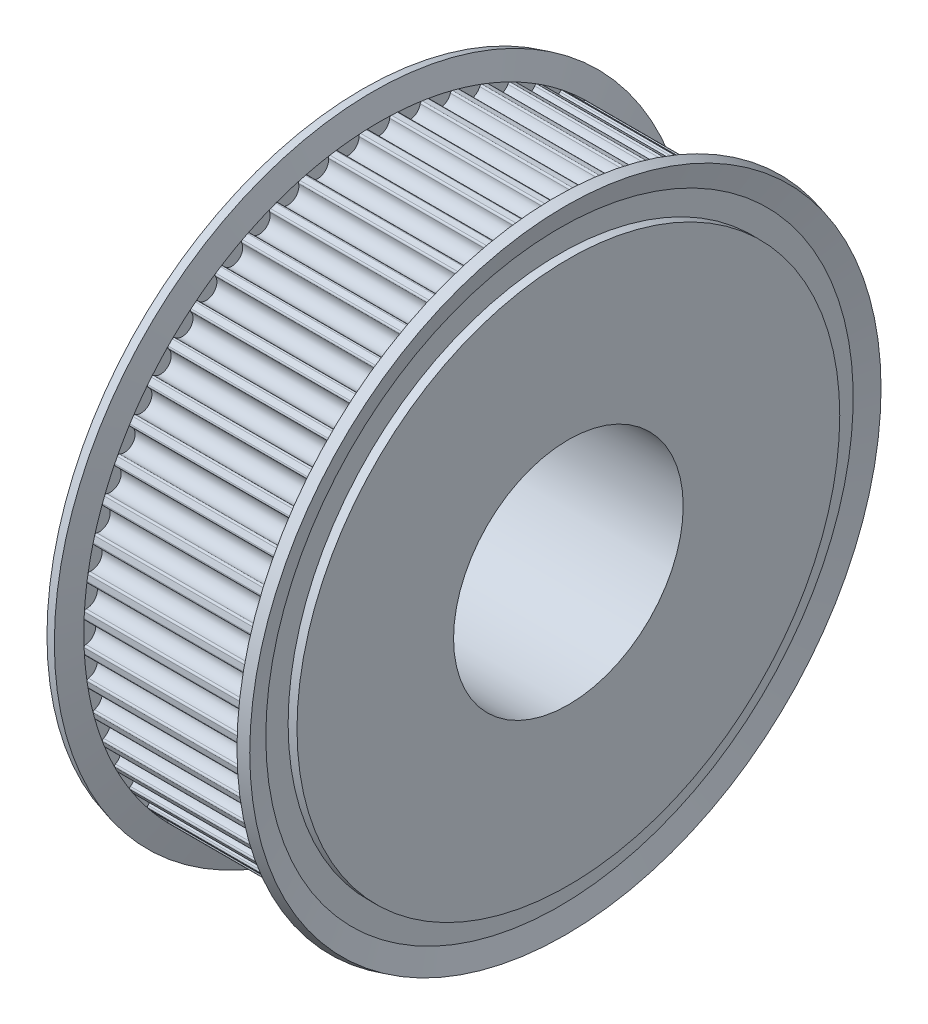
SolidWorks part; units mm, degrees
ref_plane "Front Plane" through (0, 0, 0) normal (0, 0, 1) x (1, 0, 0)
ref_plane "Top Plane" through (0, 0, 0) normal (0, 1, 0) x (1, 0, 0)
ref_plane "Right Plane" through (0, 0, 0) normal (1, 0, 0) x (0, 0, -1)
ref_plane "Plane1" through (0, 0, 0) normal (0, 0, 1) x (1, 0, 0)
sketch "Sketch1" plane through (0, 0, 0) normal (0, 0, 1) x (1, 0, 0)
  line L0 (0, 0) -> (0, 26)
  line L1 (0, 26) -> (0.85, 26)
  line L2 (0.85, 26) -> (0.85, 28.1383)
  line L3 (0.85, 28.1383) -> (0.2865, 30.2412)
  line L4 (0.2865, 30.2412) -> (1.2525, 30.5)
  line L5 (1.2525, 30.5) -> (1.85, 28.27)
  line L6 (1.85, 28.27) -> (18.15, 28.27)
  line L7 (18.15, 28.27) -> (18.7475, 30.5)
  line L8 (18.7475, 30.5) -> (19.7135, 30.2412)
  line L9 (19.7135, 30.2412) -> (19.15, 28.1383)
  line L10 (19.15, 28.1383) -> (19.15, 26)
  line L11 (19.15, 26) -> (20, 26)
  line L12 (20, 26) -> (20, 0)
  line L13 (20, 0) -> (0, 0)
  line L14 (20, 0) -> (0, 0) construction
revolve "Revolve1" add sketch "Sketch1" angle 360 about L14 reverse direction yes
ref_plane "Plane2" through (10, 0, 0) normal (1, 0, 0) x (0, 0, -1)
sketch "Sketch2" plane through (10, 0, 0) normal (1, 0, 0) x (0, 0, -1)
  line L0 (-1.2204, 28.624) -> (-1.2042, 28.2443)
  line L1 (1.2042, 28.2443) -> (1.2204, 28.624)
  arc A0 (-1.2042, 28.2443) -> (-1.0274, 28.0866) centre (-1.1969, 28.0745) cw
  arc A1 (-1.0274, 28.0866) -> (1.0274, 28.0866) centre (0, 28.16) ccw
  arc A2 (1.0274, 28.0866) -> (1.2042, 28.2443) centre (1.1969, 28.0745) cw
  arc A3 (1.2204, 28.624) -> (-1.2204, 28.624) centre (0, 0) ccw
extrude "Cut-Extrude1" cut sketch "Sketch2" against normal blind 8.15 and the other way blind 8.15
ref_plane "Plane3" through (10, 0, 0) normal (1, 0, 0) x (0, 0, -1)
sketch "Sketch3" plane through (10, 0, 0) normal (1, 0, 0) x (0, 0, -1)
  line L0 (-4.2057, 28.3396) -> (-4.1499, 27.9637)
  line L1 (-1.7547, 28.2155) -> (-1.7783, 28.5948)
  arc A0 (-4.1499, 27.9637) -> (-3.9576, 27.8254) centre (-4.125, 27.7956) cw
  arc A1 (-3.9576, 27.8254) -> (-1.9141, 28.0401) centre (-2.9435, 28.0057) ccw
  arc A2 (-1.9141, 28.0401) -> (-1.7547, 28.2155) centre (-1.7442, 28.0458) cw
  arc A3 (-1.7783, 28.5948) -> (-4.2057, 28.3396) centre (0, 0) ccw
extrude "Cut-Extrude2" cut sketch "Sketch3" against normal blind 8.15 and the other way blind 8.15
ref_plane "Plane4" through (10, 0, 0) normal (1, 0, 0) x (0, 0, -1)
sketch "Sketch4" plane through (10, 0, 0) normal (1, 0, 0) x (0, 0, -1)
  line L0 (-7.145, 27.7448) -> (-7.0502, 27.3768)
  line L1 (-4.6945, 27.8775) -> (-4.7576, 28.2522)
  arc A0 (-7.0502, 27.3768) -> (-6.8445, 27.2592) centre (-7.0078, 27.2121) cw
  arc A1 (-6.8445, 27.2592) -> (-4.8346, 27.6865) centre (-5.8548, 27.5446) ccw
  arc A2 (-4.8346, 27.6865) -> (-4.6945, 27.8775) centre (-4.6662, 27.7099) cw
  arc A3 (-4.7576, 28.2522) -> (-7.145, 27.7448) centre (0, 0) ccw
extrude "Cut-Extrude3" cut sketch "Sketch4" against normal blind 8.15 and the other way blind 8.15
ref_plane "Plane5" through (10, 0, 0) normal (1, 0, 0) x (0, 0, -1)
sketch "Sketch5" plane through (10, 0, 0) normal (1, 0, 0) x (0, 0, -1)
  line L0 (-10.0059, 26.8459) -> (-9.8732, 26.4898)
  line L1 (-7.5827, 27.2341) -> (-7.6847, 27.6002)
  arc A0 (-9.8732, 26.4898) -> (-9.6563, 26.3945) centre (-9.8139, 26.3306) cw
  arc A1 (-9.6563, 26.3945) -> (-7.7021, 27.0294) centre (-8.7019, 26.7818) ccw
  arc A2 (-7.7021, 27.0294) -> (-7.5827, 27.2341) centre (-7.5371, 27.0703) cw
  arc A3 (-7.6847, 27.6002) -> (-10.0059, 26.8459) centre (0, 0) ccw
extrude "Cut-Extrude4" cut sketch "Sketch5" against normal blind 8.15 and the other way blind 8.15
ref_plane "Plane6" through (10, 0, 0) normal (1, 0, 0) x (0, 0, -1)
sketch "Sketch6" plane through (10, 0, 0) normal (1, 0, 0) x (0, 0, -1)
  line L0 (-12.7573, 25.6529) -> (-12.5881, 25.3127)
  line L1 (-10.3879, 26.2923) -> (-10.5276, 26.6457)
  arc A0 (-12.5881, 25.3127) -> (-12.3624, 25.2405) centre (-12.5124, 25.1605) cw
  arc A1 (-12.3624, 25.2405) -> (-10.4853, 26.0763) centre (-11.4537, 25.7254) ccw
  arc A2 (-10.4853, 26.0763) -> (-10.3879, 26.2923) centre (-10.3255, 26.1342) cw
  arc A3 (-10.5276, 26.6457) -> (-12.7573, 25.6529) centre (0, 0) ccw
extrude "Cut-Extrude5" cut sketch "Sketch6" against normal blind 8.15 and the other way blind 8.15
ref_plane "Plane7" through (10, 0, 0) normal (1, 0, 0) x (0, 0, -1)
sketch "Sketch7" plane through (10, 0, 0) normal (1, 0, 0) x (0, 0, -1)
  line L0 (-15.3689, 24.1789) -> (-15.165, 23.8582)
  line L1 (-13.0793, 25.0624) -> (-13.2551, 25.3993)
  arc A0 (-15.165, 23.8582) -> (-14.933, 23.81) centre (-15.0738, 23.7148) cw
  arc A1 (-14.933, 23.81) -> (-13.1536, 24.8374) centre (-14.08, 24.3873) ccw
  arc A2 (-13.1536, 24.8374) -> (-13.0793, 25.0624) centre (-13.0007, 24.9117) cw
  arc A3 (-13.2551, 25.3993) -> (-15.3689, 24.1789) centre (0, 0) ccw
extrude "Cut-Extrude6" cut sketch "Sketch7" against normal blind 8.15 and the other way blind 8.15
ref_plane "Plane8" through (10, 0, 0) normal (1, 0, 0) x (0, 0, -1)
sketch "Sketch8" plane through (10, 0, 0) normal (1, 0, 0) x (0, 0, -1)
  line L0 (-17.8121, 22.44) -> (-17.5758, 22.1423)
  line L1 (-15.6274, 23.558) -> (-15.8375, 23.8746)
  arc A0 (-17.5758, 22.1423) -> (-17.3401, 22.1187) centre (-17.4701, 22.0092) cw
  arc A1 (-17.3401, 22.1187) -> (-15.6777, 23.3264) centre (-16.552, 22.7819) ccw
  arc A2 (-15.6777, 23.3264) -> (-15.6274, 23.558) centre (-15.5334, 23.4163) cw
  arc A3 (-15.8375, 23.8746) -> (-17.8121, 22.44) centre (0, 0) ccw
extrude "Cut-Extrude7" cut sketch "Sketch8" against normal blind 8.15 and the other way blind 8.15
ref_plane "Plane9" through (10, 0, 0) normal (1, 0, 0) x (0, 0, -1)
sketch "Sketch9" plane through (10, 0, 0) normal (1, 0, 0) x (0, 0, -1)
  line L0 (-20.0601, 20.4552) -> (-19.794, 20.1839)
  line L1 (-18.0043, 21.7954) -> (-18.2463, 22.0884)
  arc A0 (-19.794, 20.1839) -> (-19.5571, 20.185) centre (-19.675, 20.0625) cw
  arc A1 (-19.5571, 20.185) -> (-18.0301, 21.5599) centre (-18.8427, 20.927) ccw
  arc A2 (-18.0301, 21.5599) -> (-18.0043, 21.7954) centre (-17.896, 21.6643) cw
  arc A3 (-18.2463, 22.0884) -> (-20.0601, 20.4552) centre (0, 0) ccw
extrude "Cut-Extrude8" cut sketch "Sketch9" against normal blind 8.15 and the other way blind 8.15
ref_plane "Plane10" through (10, 0, 0) normal (1, 0, 0) x (0, 0, -1)
sketch "Sketch10" plane through (10, 0, 0) normal (1, 0, 0) x (0, 0, -1)
  line L0 (-22.0884, 18.2463) -> (-21.7954, 18.0043)
  line L1 (-20.1839, 19.794) -> (-20.4552, 20.0601)
  arc A0 (-21.7954, 18.0043) -> (-21.5599, 18.0301) centre (-21.6643, 17.896) cw
  arc A1 (-21.5599, 18.0301) -> (-20.185, 19.5571) centre (-20.927, 18.8427) ccw
  arc A2 (-20.185, 19.5571) -> (-20.1839, 19.794) centre (-20.0625, 19.675) cw
  arc A3 (-20.4552, 20.0601) -> (-22.0884, 18.2463) centre (0, 0) ccw
extrude "Cut-Extrude9" cut sketch "Sketch10" against normal blind 8.15 and the other way blind 8.15
ref_plane "Plane11" through (10, 0, 0) normal (1, 0, 0) x (0, 0, -1)
sketch "Sketch11" plane through (10, 0, 0) normal (1, 0, 0) x (0, 0, -1)
  line L0 (-23.8746, 15.8375) -> (-23.558, 15.6274)
  line L1 (-22.1423, 17.5758) -> (-22.44, 17.8121)
  arc A0 (-23.558, 15.6274) -> (-23.3264, 15.6777) centre (-23.4163, 15.5334) cw
  arc A1 (-23.3264, 15.6777) -> (-22.1187, 17.3401) centre (-22.7819, 16.552) ccw
  arc A2 (-22.1187, 17.3401) -> (-22.1423, 17.5758) centre (-22.0092, 17.4701) cw
  arc A3 (-22.44, 17.8121) -> (-23.8746, 15.8375) centre (0, 0) ccw
extrude "Cut-Extrude10" cut sketch "Sketch11" against normal blind 8.15 and the other way blind 8.15
ref_plane "Plane12" through (10, 0, 0) normal (1, 0, 0) x (0, 0, -1)
sketch "Sketch12" plane through (10, 0, 0) normal (1, 0, 0) x (0, 0, -1)
  line L0 (-25.3993, 13.2551) -> (-25.0624, 13.0793)
  line L1 (-23.8582, 15.165) -> (-24.1789, 15.3689)
  arc A0 (-25.0624, 13.0793) -> (-24.8374, 13.1536) centre (-24.9117, 13.0007) cw
  arc A1 (-24.8374, 13.1536) -> (-23.81, 14.933) centre (-24.3873, 14.08) ccw
  arc A2 (-23.81, 14.933) -> (-23.8582, 15.165) centre (-23.7148, 15.0738) cw
  arc A3 (-24.1789, 15.3689) -> (-25.3993, 13.2551) centre (0, 0) ccw
extrude "Cut-Extrude11" cut sketch "Sketch12" against normal blind 8.15 and the other way blind 8.15
ref_plane "Plane13" through (10, 0, 0) normal (1, 0, 0) x (0, 0, -1)
sketch "Sketch13" plane through (10, 0, 0) normal (1, 0, 0) x (0, 0, -1)
  line L0 (-26.6457, 10.5276) -> (-26.2923, 10.3879)
  line L1 (-25.3127, 12.5881) -> (-25.6529, 12.7573)
  arc A0 (-26.2923, 10.3879) -> (-26.0763, 10.4853) centre (-26.1342, 10.3255) cw
  arc A1 (-26.0763, 10.4853) -> (-25.2405, 12.3624) centre (-25.7254, 11.4537) ccw
  arc A2 (-25.2405, 12.3624) -> (-25.3127, 12.5881) centre (-25.1605, 12.5124) cw
  arc A3 (-25.6529, 12.7573) -> (-26.6457, 10.5276) centre (0, 0) ccw
extrude "Cut-Extrude12" cut sketch "Sketch13" against normal blind 8.15 and the other way blind 8.15
ref_plane "Plane14" through (10, 0, 0) normal (1, 0, 0) x (0, 0, -1)
sketch "Sketch14" plane through (10, 0, 0) normal (1, 0, 0) x (0, 0, -1)
  line L0 (-27.6002, 7.6847) -> (-27.2341, 7.5827)
  line L1 (-26.4898, 9.8732) -> (-26.8459, 10.0059)
  arc A0 (-27.2341, 7.5827) -> (-27.0294, 7.7021) centre (-27.0703, 7.5371) cw
  arc A1 (-27.0294, 7.7021) -> (-26.3945, 9.6563) centre (-26.7818, 8.7019) ccw
  arc A2 (-26.3945, 9.6563) -> (-26.4898, 9.8732) centre (-26.3306, 9.8139) cw
  arc A3 (-26.8459, 10.0059) -> (-27.6002, 7.6847) centre (0, 0) ccw
extrude "Cut-Extrude13" cut sketch "Sketch14" against normal blind 8.15 and the other way blind 8.15
ref_plane "Plane15" through (10, 0, 0) normal (1, 0, 0) x (0, 0, -1)
sketch "Sketch15" plane through (10, 0, 0) normal (1, 0, 0) x (0, 0, -1)
  line L0 (-28.2522, 4.7576) -> (-27.8775, 4.6945)
  line L1 (-27.3768, 7.0502) -> (-27.7448, 7.145)
  arc A0 (-27.8775, 4.6945) -> (-27.6865, 4.8346) centre (-27.7099, 4.6662) cw
  arc A1 (-27.6865, 4.8346) -> (-27.2592, 6.8445) centre (-27.5446, 5.8548) ccw
  arc A2 (-27.2592, 6.8445) -> (-27.3768, 7.0502) centre (-27.2121, 7.0078) cw
  arc A3 (-27.7448, 7.145) -> (-28.2522, 4.7576) centre (0, 0) ccw
extrude "Cut-Extrude14" cut sketch "Sketch15" against normal blind 8.15 and the other way blind 8.15
ref_plane "Plane16" through (10, 0, 0) normal (1, 0, 0) x (0, 0, -1)
sketch "Sketch16" plane through (10, 0, 0) normal (1, 0, 0) x (0, 0, -1)
  line L0 (-28.5948, 1.7783) -> (-28.2155, 1.7547)
  line L1 (-27.9637, 4.1499) -> (-28.3396, 4.2057)
  arc A0 (-28.2155, 1.7547) -> (-28.0401, 1.9141) centre (-28.0458, 1.7442) cw
  arc A1 (-28.0401, 1.9141) -> (-27.8254, 3.9576) centre (-28.0057, 2.9435) ccw
  arc A2 (-27.8254, 3.9576) -> (-27.9637, 4.1499) centre (-27.7956, 4.125) cw
  arc A3 (-28.3396, 4.2057) -> (-28.5948, 1.7783) centre (0, 0) ccw
extrude "Cut-Extrude15" cut sketch "Sketch16" against normal blind 8.15 and the other way blind 8.15
ref_plane "Plane17" through (10, 0, 0) normal (1, 0, 0) x (0, 0, -1)
sketch "Sketch17" plane through (10, 0, 0) normal (1, 0, 0) x (0, 0, -1)
  line L0 (-28.624, -1.2204) -> (-28.2443, -1.2042)
  line L1 (-28.2443, 1.2042) -> (-28.624, 1.2204)
  arc A0 (-28.2443, -1.2042) -> (-28.0866, -1.0274) centre (-28.0745, -1.1969) cw
  arc A1 (-28.0866, -1.0274) -> (-28.0866, 1.0274) centre (-28.16, 0) ccw
  arc A2 (-28.0866, 1.0274) -> (-28.2443, 1.2042) centre (-28.0745, 1.1969) cw
  arc A3 (-28.624, 1.2204) -> (-28.624, -1.2204) centre (0, 0) ccw
extrude "Cut-Extrude16" cut sketch "Sketch17" against normal blind 8.15 and the other way blind 8.15
ref_plane "Plane18" through (10, 0, 0) normal (1, 0, 0) x (0, 0, -1)
sketch "Sketch18" plane through (10, 0, 0) normal (1, 0, 0) x (0, 0, -1)
  line L0 (-28.3396, -4.2057) -> (-27.9637, -4.1499)
  line L1 (-28.2155, -1.7547) -> (-28.5948, -1.7783)
  arc A0 (-27.9637, -4.1499) -> (-27.8254, -3.9576) centre (-27.7956, -4.125) cw
  arc A1 (-27.8254, -3.9576) -> (-28.0401, -1.9141) centre (-28.0057, -2.9435) ccw
  arc A2 (-28.0401, -1.9141) -> (-28.2155, -1.7547) centre (-28.0458, -1.7442) cw
  arc A3 (-28.5948, -1.7783) -> (-28.3396, -4.2057) centre (0, 0) ccw
extrude "Cut-Extrude17" cut sketch "Sketch18" against normal blind 8.15 and the other way blind 8.15
ref_plane "Plane19" through (10, 0, 0) normal (1, 0, 0) x (0, 0, -1)
sketch "Sketch19" plane through (10, 0, 0) normal (1, 0, 0) x (0, 0, -1)
  line L0 (-27.7448, -7.145) -> (-27.3768, -7.0502)
  line L1 (-27.8775, -4.6945) -> (-28.2522, -4.7576)
  arc A0 (-27.3768, -7.0502) -> (-27.2592, -6.8445) centre (-27.2121, -7.0078) cw
  arc A1 (-27.2592, -6.8445) -> (-27.6865, -4.8346) centre (-27.5446, -5.8548) ccw
  arc A2 (-27.6865, -4.8346) -> (-27.8775, -4.6945) centre (-27.7099, -4.6662) cw
  arc A3 (-28.2522, -4.7576) -> (-27.7448, -7.145) centre (0, 0) ccw
extrude "Cut-Extrude18" cut sketch "Sketch19" against normal blind 8.15 and the other way blind 8.15
ref_plane "Plane20" through (10, 0, 0) normal (1, 0, 0) x (0, 0, -1)
sketch "Sketch20" plane through (10, 0, 0) normal (1, 0, 0) x (0, 0, -1)
  line L0 (-26.8459, -10.0059) -> (-26.4898, -9.8732)
  line L1 (-27.2341, -7.5827) -> (-27.6002, -7.6847)
  arc A0 (-26.4898, -9.8732) -> (-26.3945, -9.6563) centre (-26.3306, -9.8139) cw
  arc A1 (-26.3945, -9.6563) -> (-27.0294, -7.7021) centre (-26.7818, -8.7019) ccw
  arc A2 (-27.0294, -7.7021) -> (-27.2341, -7.5827) centre (-27.0703, -7.5371) cw
  arc A3 (-27.6002, -7.6847) -> (-26.8459, -10.0059) centre (0, 0) ccw
extrude "Cut-Extrude19" cut sketch "Sketch20" against normal blind 8.15 and the other way blind 8.15
ref_plane "Plane21" through (10, 0, 0) normal (1, 0, 0) x (0, 0, -1)
sketch "Sketch21" plane through (10, 0, 0) normal (1, 0, 0) x (0, 0, -1)
  line L0 (-25.6529, -12.7573) -> (-25.3127, -12.5881)
  line L1 (-26.2923, -10.3879) -> (-26.6457, -10.5276)
  arc A0 (-25.3127, -12.5881) -> (-25.2405, -12.3624) centre (-25.1605, -12.5124) cw
  arc A1 (-25.2405, -12.3624) -> (-26.0763, -10.4853) centre (-25.7254, -11.4537) ccw
  arc A2 (-26.0763, -10.4853) -> (-26.2923, -10.3879) centre (-26.1342, -10.3255) cw
  arc A3 (-26.6457, -10.5276) -> (-25.6529, -12.7573) centre (0, 0) ccw
extrude "Cut-Extrude20" cut sketch "Sketch21" against normal blind 8.15 and the other way blind 8.15
ref_plane "Plane22" through (10, 0, 0) normal (1, 0, 0) x (0, 0, -1)
sketch "Sketch22" plane through (10, 0, 0) normal (1, 0, 0) x (0, 0, -1)
  line L0 (-24.1789, -15.3689) -> (-23.8582, -15.165)
  line L1 (-25.0624, -13.0793) -> (-25.3993, -13.2551)
  arc A0 (-23.8582, -15.165) -> (-23.81, -14.933) centre (-23.7148, -15.0738) cw
  arc A1 (-23.81, -14.933) -> (-24.8374, -13.1536) centre (-24.3873, -14.08) ccw
  arc A2 (-24.8374, -13.1536) -> (-25.0624, -13.0793) centre (-24.9117, -13.0007) cw
  arc A3 (-25.3993, -13.2551) -> (-24.1789, -15.3689) centre (0, 0) ccw
extrude "Cut-Extrude21" cut sketch "Sketch22" against normal blind 8.15 and the other way blind 8.15
ref_plane "Plane23" through (10, 0, 0) normal (1, 0, 0) x (0, 0, -1)
sketch "Sketch23" plane through (10, 0, 0) normal (1, 0, 0) x (0, 0, -1)
  line L0 (-22.44, -17.8121) -> (-22.1423, -17.5758)
  line L1 (-23.558, -15.6274) -> (-23.8746, -15.8375)
  arc A0 (-22.1423, -17.5758) -> (-22.1187, -17.3401) centre (-22.0092, -17.4701) cw
  arc A1 (-22.1187, -17.3401) -> (-23.3264, -15.6777) centre (-22.7819, -16.552) ccw
  arc A2 (-23.3264, -15.6777) -> (-23.558, -15.6274) centre (-23.4163, -15.5334) cw
  arc A3 (-23.8746, -15.8375) -> (-22.44, -17.8121) centre (0, 0) ccw
extrude "Cut-Extrude22" cut sketch "Sketch23" against normal blind 8.15 and the other way blind 8.15
ref_plane "Plane24" through (10, 0, 0) normal (1, 0, 0) x (0, 0, -1)
sketch "Sketch24" plane through (10, 0, 0) normal (1, 0, 0) x (0, 0, -1)
  line L0 (-20.4552, -20.0601) -> (-20.1839, -19.794)
  line L1 (-21.7954, -18.0043) -> (-22.0884, -18.2463)
  arc A0 (-20.1839, -19.794) -> (-20.185, -19.5571) centre (-20.0625, -19.675) cw
  arc A1 (-20.185, -19.5571) -> (-21.5599, -18.0301) centre (-20.927, -18.8427) ccw
  arc A2 (-21.5599, -18.0301) -> (-21.7954, -18.0043) centre (-21.6643, -17.896) cw
  arc A3 (-22.0884, -18.2463) -> (-20.4552, -20.0601) centre (0, 0) ccw
extrude "Cut-Extrude23" cut sketch "Sketch24" against normal blind 8.15 and the other way blind 8.15
ref_plane "Plane25" through (10, 0, 0) normal (1, 0, 0) x (0, 0, -1)
sketch "Sketch25" plane through (10, 0, 0) normal (1, 0, 0) x (0, 0, -1)
  line L0 (-18.2463, -22.0884) -> (-18.0043, -21.7954)
  line L1 (-19.794, -20.1839) -> (-20.0601, -20.4552)
  arc A0 (-18.0043, -21.7954) -> (-18.0301, -21.5599) centre (-17.896, -21.6643) cw
  arc A1 (-18.0301, -21.5599) -> (-19.5571, -20.185) centre (-18.8427, -20.927) ccw
  arc A2 (-19.5571, -20.185) -> (-19.794, -20.1839) centre (-19.675, -20.0625) cw
  arc A3 (-20.0601, -20.4552) -> (-18.2463, -22.0884) centre (0, 0) ccw
extrude "Cut-Extrude24" cut sketch "Sketch25" against normal blind 8.15 and the other way blind 8.15
ref_plane "Plane26" through (10, 0, 0) normal (1, 0, 0) x (0, 0, -1)
sketch "Sketch26" plane through (10, 0, 0) normal (1, 0, 0) x (0, 0, -1)
  line L0 (-15.8375, -23.8746) -> (-15.6274, -23.558)
  line L1 (-17.5758, -22.1423) -> (-17.8121, -22.44)
  arc A0 (-15.6274, -23.558) -> (-15.6777, -23.3264) centre (-15.5334, -23.4163) cw
  arc A1 (-15.6777, -23.3264) -> (-17.3401, -22.1187) centre (-16.552, -22.7819) ccw
  arc A2 (-17.3401, -22.1187) -> (-17.5758, -22.1423) centre (-17.4701, -22.0092) cw
  arc A3 (-17.8121, -22.44) -> (-15.8375, -23.8746) centre (0, 0) ccw
extrude "Cut-Extrude25" cut sketch "Sketch26" against normal blind 8.15 and the other way blind 8.15
ref_plane "Plane27" through (10, 0, 0) normal (1, 0, 0) x (0, 0, -1)
sketch "Sketch27" plane through (10, 0, 0) normal (1, 0, 0) x (0, 0, -1)
  line L0 (-13.2551, -25.3993) -> (-13.0793, -25.0624)
  line L1 (-15.165, -23.8582) -> (-15.3689, -24.1789)
  arc A0 (-13.0793, -25.0624) -> (-13.1536, -24.8374) centre (-13.0007, -24.9117) cw
  arc A1 (-13.1536, -24.8374) -> (-14.933, -23.81) centre (-14.08, -24.3873) ccw
  arc A2 (-14.933, -23.81) -> (-15.165, -23.8582) centre (-15.0738, -23.7148) cw
  arc A3 (-15.3689, -24.1789) -> (-13.2551, -25.3993) centre (0, 0) ccw
extrude "Cut-Extrude26" cut sketch "Sketch27" against normal blind 8.15 and the other way blind 8.15
ref_plane "Plane28" through (10, 0, 0) normal (1, 0, 0) x (0, 0, -1)
sketch "Sketch28" plane through (10, 0, 0) normal (1, 0, 0) x (0, 0, -1)
  line L0 (-10.5276, -26.6457) -> (-10.3879, -26.2923)
  line L1 (-12.5881, -25.3127) -> (-12.7573, -25.6529)
  arc A0 (-10.3879, -26.2923) -> (-10.4853, -26.0763) centre (-10.3255, -26.1342) cw
  arc A1 (-10.4853, -26.0763) -> (-12.3624, -25.2405) centre (-11.4537, -25.7254) ccw
  arc A2 (-12.3624, -25.2405) -> (-12.5881, -25.3127) centre (-12.5124, -25.1605) cw
  arc A3 (-12.7573, -25.6529) -> (-10.5276, -26.6457) centre (0, 0) ccw
extrude "Cut-Extrude27" cut sketch "Sketch28" against normal blind 8.15 and the other way blind 8.15
ref_plane "Plane29" through (10, 0, 0) normal (1, 0, 0) x (0, 0, -1)
sketch "Sketch29" plane through (10, 0, 0) normal (1, 0, 0) x (0, 0, -1)
  line L0 (-7.6847, -27.6002) -> (-7.5827, -27.2341)
  line L1 (-9.8732, -26.4898) -> (-10.0059, -26.8459)
  arc A0 (-7.5827, -27.2341) -> (-7.7021, -27.0294) centre (-7.5371, -27.0703) cw
  arc A1 (-7.7021, -27.0294) -> (-9.6563, -26.3945) centre (-8.7019, -26.7818) ccw
  arc A2 (-9.6563, -26.3945) -> (-9.8732, -26.4898) centre (-9.8139, -26.3306) cw
  arc A3 (-10.0059, -26.8459) -> (-7.6847, -27.6002) centre (0, 0) ccw
extrude "Cut-Extrude28" cut sketch "Sketch29" against normal blind 8.15 and the other way blind 8.15
ref_plane "Plane30" through (10, 0, 0) normal (1, 0, 0) x (0, 0, -1)
sketch "Sketch30" plane through (10, 0, 0) normal (1, 0, 0) x (0, 0, -1)
  line L0 (-4.7576, -28.2522) -> (-4.6945, -27.8775)
  line L1 (-7.0502, -27.3768) -> (-7.145, -27.7448)
  arc A0 (-4.6945, -27.8775) -> (-4.8346, -27.6865) centre (-4.6662, -27.7099) cw
  arc A1 (-4.8346, -27.6865) -> (-6.8445, -27.2592) centre (-5.8548, -27.5446) ccw
  arc A2 (-6.8445, -27.2592) -> (-7.0502, -27.3768) centre (-7.0078, -27.2121) cw
  arc A3 (-7.145, -27.7448) -> (-4.7576, -28.2522) centre (0, 0) ccw
extrude "Cut-Extrude29" cut sketch "Sketch30" against normal blind 8.15 and the other way blind 8.15
ref_plane "Plane31" through (10, 0, 0) normal (1, 0, 0) x (0, 0, -1)
sketch "Sketch31" plane through (10, 0, 0) normal (1, 0, 0) x (0, 0, -1)
  line L0 (-1.7783, -28.5948) -> (-1.7547, -28.2155)
  line L1 (-4.1499, -27.9637) -> (-4.2057, -28.3396)
  arc A0 (-1.7547, -28.2155) -> (-1.9141, -28.0401) centre (-1.7442, -28.0458) cw
  arc A1 (-1.9141, -28.0401) -> (-3.9576, -27.8254) centre (-2.9435, -28.0057) ccw
  arc A2 (-3.9576, -27.8254) -> (-4.1499, -27.9637) centre (-4.125, -27.7956) cw
  arc A3 (-4.2057, -28.3396) -> (-1.7783, -28.5948) centre (0, 0) ccw
extrude "Cut-Extrude30" cut sketch "Sketch31" against normal blind 8.15 and the other way blind 8.15
ref_plane "Plane32" through (10, 0, 0) normal (1, 0, 0) x (0, 0, -1)
sketch "Sketch32" plane through (10, 0, 0) normal (1, 0, 0) x (0, 0, -1)
  line L0 (1.2204, -28.624) -> (1.2042, -28.2443)
  line L1 (-1.2042, -28.2443) -> (-1.2204, -28.624)
  arc A0 (1.2042, -28.2443) -> (1.0274, -28.0866) centre (1.1969, -28.0745) cw
  arc A1 (1.0274, -28.0866) -> (-1.0274, -28.0866) centre (0, -28.16) ccw
  arc A2 (-1.0274, -28.0866) -> (-1.2042, -28.2443) centre (-1.1969, -28.0745) cw
  arc A3 (-1.2204, -28.624) -> (1.2204, -28.624) centre (0, 0) ccw
extrude "Cut-Extrude31" cut sketch "Sketch32" against normal blind 8.15 and the other way blind 8.15
ref_plane "Plane33" through (10, 0, 0) normal (1, 0, 0) x (0, 0, -1)
sketch "Sketch33" plane through (10, 0, 0) normal (1, 0, 0) x (0, 0, -1)
  line L0 (4.2057, -28.3396) -> (4.1499, -27.9637)
  line L1 (1.7547, -28.2155) -> (1.7783, -28.5948)
  arc A0 (4.1499, -27.9637) -> (3.9576, -27.8254) centre (4.125, -27.7956) cw
  arc A1 (3.9576, -27.8254) -> (1.9141, -28.0401) centre (2.9435, -28.0057) ccw
  arc A2 (1.9141, -28.0401) -> (1.7547, -28.2155) centre (1.7442, -28.0458) cw
  arc A3 (1.7783, -28.5948) -> (4.2057, -28.3396) centre (0, 0) ccw
extrude "Cut-Extrude32" cut sketch "Sketch33" against normal blind 8.15 and the other way blind 8.15
ref_plane "Plane34" through (10, 0, 0) normal (1, 0, 0) x (0, 0, -1)
sketch "Sketch34" plane through (10, 0, 0) normal (1, 0, 0) x (0, 0, -1)
  line L0 (7.145, -27.7448) -> (7.0502, -27.3768)
  line L1 (4.6945, -27.8775) -> (4.7576, -28.2522)
  arc A0 (7.0502, -27.3768) -> (6.8445, -27.2592) centre (7.0078, -27.2121) cw
  arc A1 (6.8445, -27.2592) -> (4.8346, -27.6865) centre (5.8548, -27.5446) ccw
  arc A2 (4.8346, -27.6865) -> (4.6945, -27.8775) centre (4.6662, -27.7099) cw
  arc A3 (4.7576, -28.2522) -> (7.145, -27.7448) centre (0, 0) ccw
extrude "Cut-Extrude33" cut sketch "Sketch34" against normal blind 8.15 and the other way blind 8.15
ref_plane "Plane35" through (10, 0, 0) normal (1, 0, 0) x (0, 0, -1)
sketch "Sketch35" plane through (10, 0, 0) normal (1, 0, 0) x (0, 0, -1)
  line L0 (10.0059, -26.8459) -> (9.8732, -26.4898)
  line L1 (7.5827, -27.2341) -> (7.6847, -27.6002)
  arc A0 (9.8732, -26.4898) -> (9.6563, -26.3945) centre (9.8139, -26.3306) cw
  arc A1 (9.6563, -26.3945) -> (7.7021, -27.0294) centre (8.7019, -26.7818) ccw
  arc A2 (7.7021, -27.0294) -> (7.5827, -27.2341) centre (7.5371, -27.0703) cw
  arc A3 (7.6847, -27.6002) -> (10.0059, -26.8459) centre (0, 0) ccw
extrude "Cut-Extrude34" cut sketch "Sketch35" against normal blind 8.15 and the other way blind 8.15
ref_plane "Plane36" through (10, 0, 0) normal (1, 0, 0) x (0, 0, -1)
sketch "Sketch36" plane through (10, 0, 0) normal (1, 0, 0) x (0, 0, -1)
  line L0 (12.7573, -25.6529) -> (12.5881, -25.3127)
  line L1 (10.3879, -26.2923) -> (10.5276, -26.6457)
  arc A0 (12.5881, -25.3127) -> (12.3624, -25.2405) centre (12.5124, -25.1605) cw
  arc A1 (12.3624, -25.2405) -> (10.4853, -26.0763) centre (11.4537, -25.7254) ccw
  arc A2 (10.4853, -26.0763) -> (10.3879, -26.2923) centre (10.3255, -26.1342) cw
  arc A3 (10.5276, -26.6457) -> (12.7573, -25.6529) centre (0, 0) ccw
extrude "Cut-Extrude35" cut sketch "Sketch36" against normal blind 8.15 and the other way blind 8.15
ref_plane "Plane37" through (10, 0, 0) normal (1, 0, 0) x (0, 0, -1)
sketch "Sketch37" plane through (10, 0, 0) normal (1, 0, 0) x (0, 0, -1)
  line L0 (15.3689, -24.1789) -> (15.165, -23.8582)
  line L1 (13.0793, -25.0624) -> (13.2551, -25.3993)
  arc A0 (15.165, -23.8582) -> (14.933, -23.81) centre (15.0738, -23.7148) cw
  arc A1 (14.933, -23.81) -> (13.1536, -24.8374) centre (14.08, -24.3873) ccw
  arc A2 (13.1536, -24.8374) -> (13.0793, -25.0624) centre (13.0007, -24.9117) cw
  arc A3 (13.2551, -25.3993) -> (15.3689, -24.1789) centre (0, 0) ccw
extrude "Cut-Extrude36" cut sketch "Sketch37" against normal blind 8.15 and the other way blind 8.15
ref_plane "Plane38" through (10, 0, 0) normal (1, 0, 0) x (0, 0, -1)
sketch "Sketch38" plane through (10, 0, 0) normal (1, 0, 0) x (0, 0, -1)
  line L0 (17.8121, -22.44) -> (17.5758, -22.1423)
  line L1 (15.6274, -23.558) -> (15.8375, -23.8746)
  arc A0 (17.5758, -22.1423) -> (17.3401, -22.1187) centre (17.4701, -22.0092) cw
  arc A1 (17.3401, -22.1187) -> (15.6777, -23.3264) centre (16.552, -22.7819) ccw
  arc A2 (15.6777, -23.3264) -> (15.6274, -23.558) centre (15.5334, -23.4163) cw
  arc A3 (15.8375, -23.8746) -> (17.8121, -22.44) centre (0, 0) ccw
extrude "Cut-Extrude37" cut sketch "Sketch38" against normal blind 8.15 and the other way blind 8.15
ref_plane "Plane39" through (10, 0, 0) normal (1, 0, 0) x (0, 0, -1)
sketch "Sketch39" plane through (10, 0, 0) normal (1, 0, 0) x (0, 0, -1)
  line L0 (20.0601, -20.4552) -> (19.794, -20.1839)
  line L1 (18.0043, -21.7954) -> (18.2463, -22.0884)
  arc A0 (19.794, -20.1839) -> (19.5571, -20.185) centre (19.675, -20.0625) cw
  arc A1 (19.5571, -20.185) -> (18.0301, -21.5599) centre (18.8427, -20.927) ccw
  arc A2 (18.0301, -21.5599) -> (18.0043, -21.7954) centre (17.896, -21.6643) cw
  arc A3 (18.2463, -22.0884) -> (20.0601, -20.4552) centre (0, 0) ccw
extrude "Cut-Extrude38" cut sketch "Sketch39" against normal blind 8.15 and the other way blind 8.15
ref_plane "Plane40" through (10, 0, 0) normal (1, 0, 0) x (0, 0, -1)
sketch "Sketch40" plane through (10, 0, 0) normal (1, 0, 0) x (0, 0, -1)
  line L0 (22.0884, -18.2463) -> (21.7954, -18.0043)
  line L1 (20.1839, -19.794) -> (20.4552, -20.0601)
  arc A0 (21.7954, -18.0043) -> (21.5599, -18.0301) centre (21.6643, -17.896) cw
  arc A1 (21.5599, -18.0301) -> (20.185, -19.5571) centre (20.927, -18.8427) ccw
  arc A2 (20.185, -19.5571) -> (20.1839, -19.794) centre (20.0625, -19.675) cw
  arc A3 (20.4552, -20.0601) -> (22.0884, -18.2463) centre (0, 0) ccw
extrude "Cut-Extrude39" cut sketch "Sketch40" against normal blind 8.15 and the other way blind 8.15
ref_plane "Plane41" through (10, 0, 0) normal (1, 0, 0) x (0, 0, -1)
sketch "Sketch41" plane through (10, 0, 0) normal (1, 0, 0) x (0, 0, -1)
  line L0 (23.8746, -15.8375) -> (23.558, -15.6274)
  line L1 (22.1423, -17.5758) -> (22.44, -17.8121)
  arc A0 (23.558, -15.6274) -> (23.3264, -15.6777) centre (23.4163, -15.5334) cw
  arc A1 (23.3264, -15.6777) -> (22.1187, -17.3401) centre (22.7819, -16.552) ccw
  arc A2 (22.1187, -17.3401) -> (22.1423, -17.5758) centre (22.0092, -17.4701) cw
  arc A3 (22.44, -17.8121) -> (23.8746, -15.8375) centre (0, 0) ccw
extrude "Cut-Extrude40" cut sketch "Sketch41" against normal blind 8.15 and the other way blind 8.15
ref_plane "Plane42" through (10, 0, 0) normal (1, 0, 0) x (0, 0, -1)
sketch "Sketch42" plane through (10, 0, 0) normal (1, 0, 0) x (0, 0, -1)
  line L0 (25.3993, -13.2551) -> (25.0624, -13.0793)
  line L1 (23.8582, -15.165) -> (24.1789, -15.3689)
  arc A0 (25.0624, -13.0793) -> (24.8374, -13.1536) centre (24.9117, -13.0007) cw
  arc A1 (24.8374, -13.1536) -> (23.81, -14.933) centre (24.3873, -14.08) ccw
  arc A2 (23.81, -14.933) -> (23.8582, -15.165) centre (23.7148, -15.0738) cw
  arc A3 (24.1789, -15.3689) -> (25.3993, -13.2551) centre (0, 0) ccw
extrude "Cut-Extrude41" cut sketch "Sketch42" against normal blind 8.15 and the other way blind 8.15
ref_plane "Plane43" through (10, 0, 0) normal (1, 0, 0) x (0, 0, -1)
sketch "Sketch43" plane through (10, 0, 0) normal (1, 0, 0) x (0, 0, -1)
  line L0 (26.6457, -10.5276) -> (26.2923, -10.3879)
  line L1 (25.3127, -12.5881) -> (25.6529, -12.7573)
  arc A0 (26.2923, -10.3879) -> (26.0763, -10.4853) centre (26.1342, -10.3255) cw
  arc A1 (26.0763, -10.4853) -> (25.2405, -12.3624) centre (25.7254, -11.4537) ccw
  arc A2 (25.2405, -12.3624) -> (25.3127, -12.5881) centre (25.1605, -12.5124) cw
  arc A3 (25.6529, -12.7573) -> (26.6457, -10.5276) centre (0, 0) ccw
extrude "Cut-Extrude42" cut sketch "Sketch43" against normal blind 8.15 and the other way blind 8.15
ref_plane "Plane44" through (10, 0, 0) normal (1, 0, 0) x (0, 0, -1)
sketch "Sketch44" plane through (10, 0, 0) normal (1, 0, 0) x (0, 0, -1)
  line L0 (27.6002, -7.6847) -> (27.2341, -7.5827)
  line L1 (26.4898, -9.8732) -> (26.8459, -10.0059)
  arc A0 (27.2341, -7.5827) -> (27.0294, -7.7021) centre (27.0703, -7.5371) cw
  arc A1 (27.0294, -7.7021) -> (26.3945, -9.6563) centre (26.7818, -8.7019) ccw
  arc A2 (26.3945, -9.6563) -> (26.4898, -9.8732) centre (26.3306, -9.8139) cw
  arc A3 (26.8459, -10.0059) -> (27.6002, -7.6847) centre (0, 0) ccw
extrude "Cut-Extrude43" cut sketch "Sketch44" against normal blind 8.15 and the other way blind 8.15
ref_plane "Plane45" through (10, 0, 0) normal (1, 0, 0) x (0, 0, -1)
sketch "Sketch45" plane through (10, 0, 0) normal (1, 0, 0) x (0, 0, -1)
  line L0 (28.2522, -4.7576) -> (27.8775, -4.6945)
  line L1 (27.3768, -7.0502) -> (27.7448, -7.145)
  arc A0 (27.8775, -4.6945) -> (27.6865, -4.8346) centre (27.7099, -4.6662) cw
  arc A1 (27.6865, -4.8346) -> (27.2592, -6.8445) centre (27.5446, -5.8548) ccw
  arc A2 (27.2592, -6.8445) -> (27.3768, -7.0502) centre (27.2121, -7.0078) cw
  arc A3 (27.7448, -7.145) -> (28.2522, -4.7576) centre (0, 0) ccw
extrude "Cut-Extrude44" cut sketch "Sketch45" against normal blind 8.15 and the other way blind 8.15
ref_plane "Plane46" through (10, 0, 0) normal (1, 0, 0) x (0, 0, -1)
sketch "Sketch46" plane through (10, 0, 0) normal (1, 0, 0) x (0, 0, -1)
  line L0 (28.5948, -1.7783) -> (28.2155, -1.7547)
  line L1 (27.9637, -4.1499) -> (28.3396, -4.2057)
  arc A0 (28.2155, -1.7547) -> (28.0401, -1.9141) centre (28.0458, -1.7442) cw
  arc A1 (28.0401, -1.9141) -> (27.8254, -3.9576) centre (28.0057, -2.9435) ccw
  arc A2 (27.8254, -3.9576) -> (27.9637, -4.1499) centre (27.7956, -4.125) cw
  arc A3 (28.3396, -4.2057) -> (28.5948, -1.7783) centre (0, 0) ccw
extrude "Cut-Extrude45" cut sketch "Sketch46" against normal blind 8.15 and the other way blind 8.15
ref_plane "Plane47" through (10, 0, 0) normal (1, 0, 0) x (0, 0, -1)
sketch "Sketch47" plane through (10, 0, 0) normal (1, 0, 0) x (0, 0, -1)
  line L0 (28.624, 1.2204) -> (28.2443, 1.2042)
  line L1 (28.2443, -1.2042) -> (28.624, -1.2204)
  arc A0 (28.2443, 1.2042) -> (28.0866, 1.0274) centre (28.0745, 1.1969) cw
  arc A1 (28.0866, 1.0274) -> (28.0866, -1.0274) centre (28.16, 0) ccw
  arc A2 (28.0866, -1.0274) -> (28.2443, -1.2042) centre (28.0745, -1.1969) cw
  arc A3 (28.624, -1.2204) -> (28.624, 1.2204) centre (0, 0) ccw
extrude "Cut-Extrude46" cut sketch "Sketch47" against normal blind 8.15 and the other way blind 8.15
ref_plane "Plane48" through (10, 0, 0) normal (1, 0, 0) x (0, 0, -1)
sketch "Sketch48" plane through (10, 0, 0) normal (1, 0, 0) x (0, 0, -1)
  line L0 (28.3396, 4.2057) -> (27.9637, 4.1499)
  line L1 (28.2155, 1.7547) -> (28.5948, 1.7783)
  arc A0 (27.9637, 4.1499) -> (27.8254, 3.9576) centre (27.7956, 4.125) cw
  arc A1 (27.8254, 3.9576) -> (28.0401, 1.9141) centre (28.0057, 2.9435) ccw
  arc A2 (28.0401, 1.9141) -> (28.2155, 1.7547) centre (28.0458, 1.7442) cw
  arc A3 (28.5948, 1.7783) -> (28.3396, 4.2057) centre (0, 0) ccw
extrude "Cut-Extrude47" cut sketch "Sketch48" against normal blind 8.15 and the other way blind 8.15
ref_plane "Plane49" through (10, 0, 0) normal (1, 0, 0) x (0, 0, -1)
sketch "Sketch49" plane through (10, 0, 0) normal (1, 0, 0) x (0, 0, -1)
  line L0 (27.7448, 7.145) -> (27.3768, 7.0502)
  line L1 (27.8775, 4.6945) -> (28.2522, 4.7576)
  arc A0 (27.3768, 7.0502) -> (27.2592, 6.8445) centre (27.2121, 7.0078) cw
  arc A1 (27.2592, 6.8445) -> (27.6865, 4.8346) centre (27.5446, 5.8548) ccw
  arc A2 (27.6865, 4.8346) -> (27.8775, 4.6945) centre (27.7099, 4.6662) cw
  arc A3 (28.2522, 4.7576) -> (27.7448, 7.145) centre (0, 0) ccw
extrude "Cut-Extrude48" cut sketch "Sketch49" against normal blind 8.15 and the other way blind 8.15
ref_plane "Plane50" through (10, 0, 0) normal (1, 0, 0) x (0, 0, -1)
sketch "Sketch50" plane through (10, 0, 0) normal (1, 0, 0) x (0, 0, -1)
  line L0 (26.8459, 10.0059) -> (26.4898, 9.8732)
  line L1 (27.2341, 7.5827) -> (27.6002, 7.6847)
  arc A0 (26.4898, 9.8732) -> (26.3945, 9.6563) centre (26.3306, 9.8139) cw
  arc A1 (26.3945, 9.6563) -> (27.0294, 7.7021) centre (26.7818, 8.7019) ccw
  arc A2 (27.0294, 7.7021) -> (27.2341, 7.5827) centre (27.0703, 7.5371) cw
  arc A3 (27.6002, 7.6847) -> (26.8459, 10.0059) centre (0, 0) ccw
extrude "Cut-Extrude49" cut sketch "Sketch50" against normal blind 8.15 and the other way blind 8.15
ref_plane "Plane51" through (10, 0, 0) normal (1, 0, 0) x (0, 0, -1)
sketch "Sketch51" plane through (10, 0, 0) normal (1, 0, 0) x (0, 0, -1)
  line L0 (25.6529, 12.7573) -> (25.3127, 12.5881)
  line L1 (26.2923, 10.3879) -> (26.6457, 10.5276)
  arc A0 (25.3127, 12.5881) -> (25.2405, 12.3624) centre (25.1605, 12.5124) cw
  arc A1 (25.2405, 12.3624) -> (26.0763, 10.4853) centre (25.7254, 11.4537) ccw
  arc A2 (26.0763, 10.4853) -> (26.2923, 10.3879) centre (26.1342, 10.3255) cw
  arc A3 (26.6457, 10.5276) -> (25.6529, 12.7573) centre (0, 0) ccw
extrude "Cut-Extrude50" cut sketch "Sketch51" against normal blind 8.15 and the other way blind 8.15
ref_plane "Plane52" through (10, 0, 0) normal (1, 0, 0) x (0, 0, -1)
sketch "Sketch52" plane through (10, 0, 0) normal (1, 0, 0) x (0, 0, -1)
  line L0 (24.1789, 15.3689) -> (23.8582, 15.165)
  line L1 (25.0624, 13.0793) -> (25.3993, 13.2551)
  arc A0 (23.8582, 15.165) -> (23.81, 14.933) centre (23.7148, 15.0738) cw
  arc A1 (23.81, 14.933) -> (24.8374, 13.1536) centre (24.3873, 14.08) ccw
  arc A2 (24.8374, 13.1536) -> (25.0624, 13.0793) centre (24.9117, 13.0007) cw
  arc A3 (25.3993, 13.2551) -> (24.1789, 15.3689) centre (0, 0) ccw
extrude "Cut-Extrude51" cut sketch "Sketch52" against normal blind 8.15 and the other way blind 8.15
ref_plane "Plane53" through (10, 0, 0) normal (1, 0, 0) x (0, 0, -1)
sketch "Sketch53" plane through (10, 0, 0) normal (1, 0, 0) x (0, 0, -1)
  line L0 (22.44, 17.8121) -> (22.1423, 17.5758)
  line L1 (23.558, 15.6274) -> (23.8746, 15.8375)
  arc A0 (22.1423, 17.5758) -> (22.1187, 17.3401) centre (22.0092, 17.4701) cw
  arc A1 (22.1187, 17.3401) -> (23.3264, 15.6777) centre (22.7819, 16.552) ccw
  arc A2 (23.3264, 15.6777) -> (23.558, 15.6274) centre (23.4163, 15.5334) cw
  arc A3 (23.8746, 15.8375) -> (22.44, 17.8121) centre (0, 0) ccw
extrude "Cut-Extrude52" cut sketch "Sketch53" against normal blind 8.15 and the other way blind 8.15
ref_plane "Plane54" through (10, 0, 0) normal (1, 0, 0) x (0, 0, -1)
sketch "Sketch54" plane through (10, 0, 0) normal (1, 0, 0) x (0, 0, -1)
  line L0 (20.4552, 20.0601) -> (20.1839, 19.794)
  line L1 (21.7954, 18.0043) -> (22.0884, 18.2463)
  arc A0 (20.1839, 19.794) -> (20.185, 19.5571) centre (20.0625, 19.675) cw
  arc A1 (20.185, 19.5571) -> (21.5599, 18.0301) centre (20.927, 18.8427) ccw
  arc A2 (21.5599, 18.0301) -> (21.7954, 18.0043) centre (21.6643, 17.896) cw
  arc A3 (22.0884, 18.2463) -> (20.4552, 20.0601) centre (0, 0) ccw
extrude "Cut-Extrude53" cut sketch "Sketch54" against normal blind 8.15 and the other way blind 8.15
ref_plane "Plane55" through (10, 0, 0) normal (1, 0, 0) x (0, 0, -1)
sketch "Sketch55" plane through (10, 0, 0) normal (1, 0, 0) x (0, 0, -1)
  line L0 (18.2463, 22.0884) -> (18.0043, 21.7954)
  line L1 (19.794, 20.1839) -> (20.0601, 20.4552)
  arc A0 (18.0043, 21.7954) -> (18.0301, 21.5599) centre (17.896, 21.6643) cw
  arc A1 (18.0301, 21.5599) -> (19.5571, 20.185) centre (18.8427, 20.927) ccw
  arc A2 (19.5571, 20.185) -> (19.794, 20.1839) centre (19.675, 20.0625) cw
  arc A3 (20.0601, 20.4552) -> (18.2463, 22.0884) centre (0, 0) ccw
extrude "Cut-Extrude54" cut sketch "Sketch55" against normal blind 8.15 and the other way blind 8.15
ref_plane "Plane56" through (10, 0, 0) normal (1, 0, 0) x (0, 0, -1)
sketch "Sketch56" plane through (10, 0, 0) normal (1, 0, 0) x (0, 0, -1)
  line L0 (15.8375, 23.8746) -> (15.6274, 23.558)
  line L1 (17.5758, 22.1423) -> (17.8121, 22.44)
  arc A0 (15.6274, 23.558) -> (15.6777, 23.3264) centre (15.5334, 23.4163) cw
  arc A1 (15.6777, 23.3264) -> (17.3401, 22.1187) centre (16.552, 22.7819) ccw
  arc A2 (17.3401, 22.1187) -> (17.5758, 22.1423) centre (17.4701, 22.0092) cw
  arc A3 (17.8121, 22.44) -> (15.8375, 23.8746) centre (0, 0) ccw
extrude "Cut-Extrude55" cut sketch "Sketch56" against normal blind 8.15 and the other way blind 8.15
ref_plane "Plane57" through (10, 0, 0) normal (1, 0, 0) x (0, 0, -1)
sketch "Sketch57" plane through (10, 0, 0) normal (1, 0, 0) x (0, 0, -1)
  line L0 (13.2551, 25.3993) -> (13.0793, 25.0624)
  line L1 (15.165, 23.8582) -> (15.3689, 24.1789)
  arc A0 (13.0793, 25.0624) -> (13.1536, 24.8374) centre (13.0007, 24.9117) cw
  arc A1 (13.1536, 24.8374) -> (14.933, 23.81) centre (14.08, 24.3873) ccw
  arc A2 (14.933, 23.81) -> (15.165, 23.8582) centre (15.0738, 23.7148) cw
  arc A3 (15.3689, 24.1789) -> (13.2551, 25.3993) centre (0, 0) ccw
extrude "Cut-Extrude56" cut sketch "Sketch57" against normal blind 8.15 and the other way blind 8.15
ref_plane "Plane58" through (10, 0, 0) normal (1, 0, 0) x (0, 0, -1)
sketch "Sketch58" plane through (10, 0, 0) normal (1, 0, 0) x (0, 0, -1)
  line L0 (10.5276, 26.6457) -> (10.3879, 26.2923)
  line L1 (12.5881, 25.3127) -> (12.7573, 25.6529)
  arc A0 (10.3879, 26.2923) -> (10.4853, 26.0763) centre (10.3255, 26.1342) cw
  arc A1 (10.4853, 26.0763) -> (12.3624, 25.2405) centre (11.4537, 25.7254) ccw
  arc A2 (12.3624, 25.2405) -> (12.5881, 25.3127) centre (12.5124, 25.1605) cw
  arc A3 (12.7573, 25.6529) -> (10.5276, 26.6457) centre (0, 0) ccw
extrude "Cut-Extrude57" cut sketch "Sketch58" against normal blind 8.15 and the other way blind 8.15
ref_plane "Plane59" through (10, 0, 0) normal (1, 0, 0) x (0, 0, -1)
sketch "Sketch59" plane through (10, 0, 0) normal (1, 0, 0) x (0, 0, -1)
  line L0 (7.6847, 27.6002) -> (7.5827, 27.2341)
  line L1 (9.8732, 26.4898) -> (10.0059, 26.8459)
  arc A0 (7.5827, 27.2341) -> (7.7021, 27.0294) centre (7.5371, 27.0703) cw
  arc A1 (7.7021, 27.0294) -> (9.6563, 26.3945) centre (8.7019, 26.7818) ccw
  arc A2 (9.6563, 26.3945) -> (9.8732, 26.4898) centre (9.8139, 26.3306) cw
  arc A3 (10.0059, 26.8459) -> (7.6847, 27.6002) centre (0, 0) ccw
extrude "Cut-Extrude58" cut sketch "Sketch59" against normal blind 8.15 and the other way blind 8.15
ref_plane "Plane60" through (10, 0, 0) normal (1, 0, 0) x (0, 0, -1)
sketch "Sketch60" plane through (10, 0, 0) normal (1, 0, 0) x (0, 0, -1)
  line L0 (4.7576, 28.2522) -> (4.6945, 27.8775)
  line L1 (7.0502, 27.3768) -> (7.145, 27.7448)
  arc A0 (4.6945, 27.8775) -> (4.8346, 27.6865) centre (4.6662, 27.7099) cw
  arc A1 (4.8346, 27.6865) -> (6.8445, 27.2592) centre (5.8548, 27.5446) ccw
  arc A2 (6.8445, 27.2592) -> (7.0502, 27.3768) centre (7.0078, 27.2121) cw
  arc A3 (7.145, 27.7448) -> (4.7576, 28.2522) centre (0, 0) ccw
extrude "Cut-Extrude59" cut sketch "Sketch60" against normal blind 8.15 and the other way blind 8.15
ref_plane "Plane61" through (10, 0, 0) normal (1, 0, 0) x (0, 0, -1)
sketch "Sketch61" plane through (10, 0, 0) normal (1, 0, 0) x (0, 0, -1)
  line L0 (1.7783, 28.5948) -> (1.7547, 28.2155)
  line L1 (4.1499, 27.9637) -> (4.2057, 28.3396)
  arc A0 (1.7547, 28.2155) -> (1.9141, 28.0401) centre (1.7442, 28.0458) cw
  arc A1 (1.9141, 28.0401) -> (3.9576, 27.8254) centre (2.9435, 28.0057) ccw
  arc A2 (3.9576, 27.8254) -> (4.1499, 27.9637) centre (4.125, 27.7956) cw
  arc A3 (4.2057, 28.3396) -> (1.7783, 28.5948) centre (0, 0) ccw
extrude "Cut-Extrude60" cut sketch "Sketch61" against normal blind 8.15 and the other way blind 8.15
ref_plane "Plane62" through (0, 0, 0) normal (0, 0, 1) x (1, 0, 0)
sketch "Sketch62" plane through (0, 0, 0) normal (0, 0, 1) x (1, 0, 0)
  line L0 (0, 0) -> (0, 11)
  line L1 (0, 11) -> (20, 11)
  line L2 (20, 11) -> (20, 0)
  line L3 (20, 0) -> (0, 0)
  line L4 (20, 0) -> (0, 0) construction
revolve "Cut-Revolve1" cut sketch "Sketch62" angle 360 about L4 reverse direction yes
